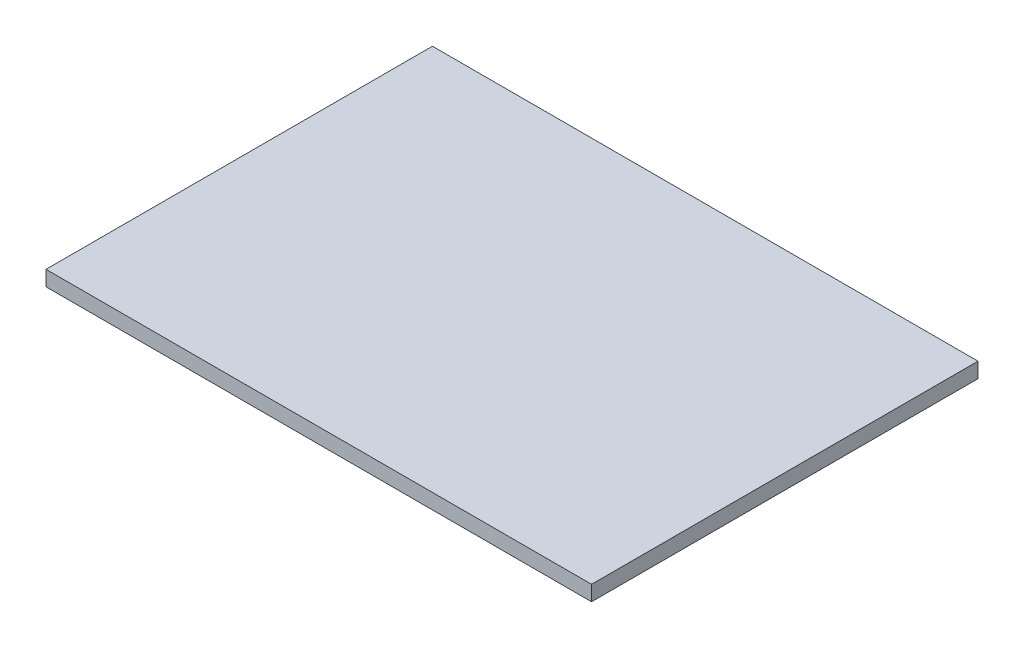
SolidWorks part; units mm, degrees
ref_plane "Front Plane" through (0, 0, 0) normal (0, 0, 1) x (1, 0, 0)
ref_plane "Top Plane" through (0, 0, 0) normal (0, 1, 0) x (1, 0, 0)
ref_plane "Right Plane" through (0, 0, 0) normal (1, 0, 0) x (0, 0, -1)
sketch "Sketch1" plane through (0, 0, 0) normal (0, 1, 0) x (1, 0, 0)
  line L1 (-18, 12.75) -> (18, 12.75)
  line L2 (-18, 12.75) -> (-18, -12.75)
  line L3 (-18, -12.75) -> (18, -12.75)
  line L4 (18, 12.75) -> (18, -12.75)
  line L5 (-18, 12.75) -> (18, -12.75) construction
  line L6 (-18, -12.75) -> (18, 12.75) construction
  point P0 (0, 0)
  dimension "D1" = 36
  dimension "D2" = 25.5
extrude "Boss-Extrude1" add sketch "Sketch1" along normal blind 1
ref_axis "Axis1" through (0, 1, 12.75) along (0, 0, -1)
ref_axis "Axis2" through (-18, 1, 0) along (1, 0, 0)
ref_plane "Plane1" through (-0.5, 0.5, 0) normal (0.7071, -0.7071, 0) x (-0.7071, -0.7071, 0)
ref_plane "Plane2" through (0.5, 0.5, 0) normal (0.7071, 0.7071, 0) x (0.7071, -0.7071, 0)
ref_axis "Axis3" through (-9.9, 10.9, 0) along (0.7071, -0.7071, 0)
ref_axis "Axis4" through (9.9, 10.9, 0) along (-0.7071, -0.7071, 0)
